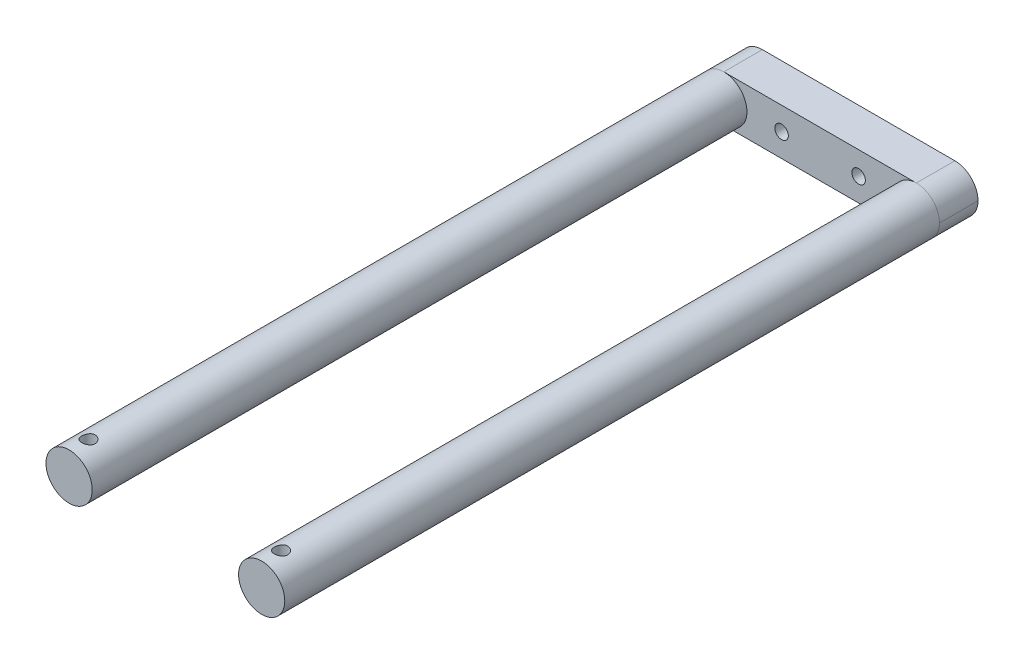
SolidWorks part; units mm, degrees
ref_plane "Front Plane" through (0, 0, 0) normal (0, 0, 1) x (1, 0, 0)
ref_plane "Top Plane" through (0, 0, 0) normal (0, 1, 0) x (1, 0, 0)
ref_plane "Right Plane" through (0, 0, 0) normal (1, 0, 0) x (0, 0, -1)
sketch "Sketch1" plane through (0, 0, 0) normal (0, 0, 1) x (1, 0, 0)
  line L1 (-31, 6) -> (31, 6)
  line L2 (-31, 6) -> (-31, -6)
  line L3 (-31, -6) -> (31, -6)
  line L4 (31, 6) -> (31, -6)
  line L5 (-31, 6) -> (31, -6) construction
  line L6 (-31, -6) -> (31, 6) construction
  point P0 (0, 0)
  dimension "D1" = 62
  dimension "D2" = 12
extrude "Boss-Extrude1" add sketch "Sketch1" along normal blind 10
sketch "Sketch2" plane through (0, 0, 10) normal (0, 0, 1) x (1, 0, 0)
  circle A0 centre (-25, 0) radius 6
  circle A1 centre (25, 0) radius 6
  dimension "D3" = 12
  dimension "D1" = 25
  dimension "D2" = 25
extrude "Boss-Extrude2" add sketch "Sketch2" along normal blind 170
fillet "Fillet1" radius 6 4 edges at (-31, -6, 5) (-31, 6, 5) (31, 6, 5) (31, -6, 5)
sketch "Sketch6" plane through (0, 0, 0) normal (0, 1, 0) x (1, 0, 0)
  line L0 (-31, -180) -> (-19, -180) construction
  circle A0 centre (-25, -175) radius 1.75
  circle A1 centre (25, -175) radius 1.75
  dimension "D2" = 3.5
  dimension "D1" = 5
extrude "Cut-Extrude3" cut sketch "Sketch6" against normal through all both and the other way through all
sketch "Sketch7" plane through (0, 0, 0) normal (0, 0, -1) x (-1, 0, 0)
  circle A0 centre (-10, 0) radius 1.75
  circle A1 centre (10, 0) radius 1.75
  dimension "D1" = 3.5
  dimension "D2" = 10
  dimension "D3" = 10
extrude "Cut-Extrude4" cut sketch "Sketch7" against normal up to next
